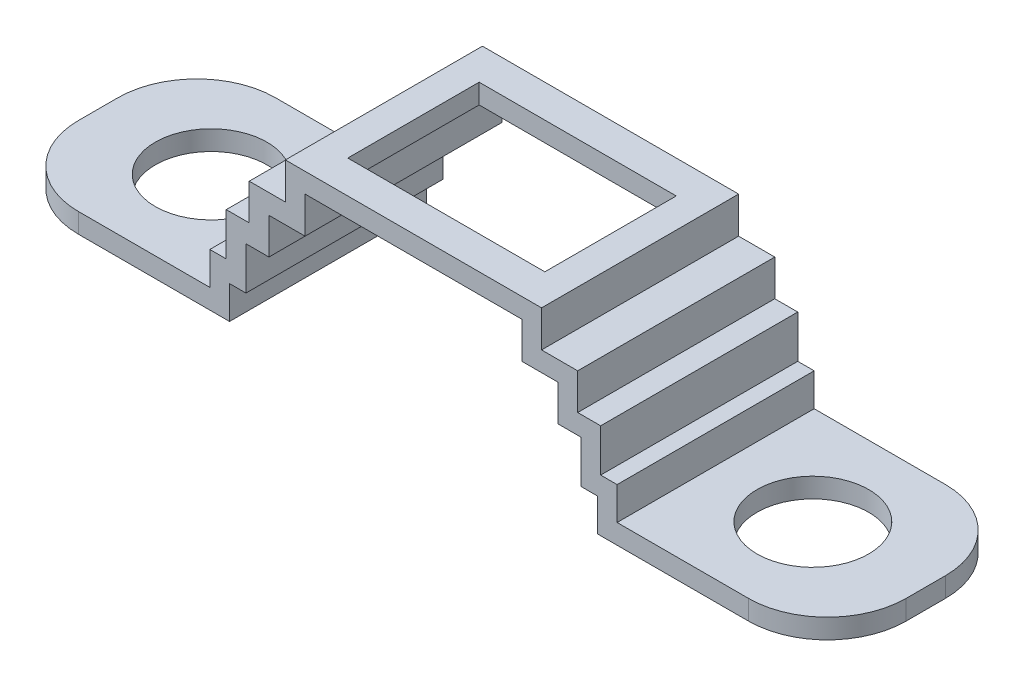
SolidWorks part; units mm, degrees
material "PBT General Purpose"
ref_plane "Front Plane" through (0, 0, 0) normal (0, 0, 1) x (1, 0, 0)
ref_plane "Top Plane" through (0, 0, 0) normal (0, 1, 0) x (1, 0, 0)
ref_plane "Right Plane" through (0, 0, 0) normal (1, 0, 0) x (0, 0, -1)
sketch "Sketch1" plane through (0, 0, 0) normal (0, 0, 1) x (1, 0, 0)
  line L0 (-63, 4.5) -> (-28, 4.5)
  line L1 (-28, 4.5) -> (-28, 9.5)
  line L2 (-28, 9.5) -> (-25.5, 9.5)
  line L3 (-25.5, 9.5) -> (-25.5, 16)
  line L4 (-25.5, 16) -> (-22, 16)
  line L5 (-22, 16) -> (-22, 21.5)
  line L6 (-22, 21.5) -> (-16.5, 21.5)
  line L7 (-16.5, 21.5) -> (-16.5, 27.05)
  line L8 (-16.5, 27.05) -> (0, 27.05)
  circle A0 centre (0, 0) radius 27.05
  dimension "D1" = 54.1
  dimension "D2" = 35
  dimension "D3" = 4.5
  dimension "D4" = 28
  dimension "D5" = 5
  dimension "D6" = 2.5
  dimension "D7" = 6.5
  dimension "D8" = 3.5
  dimension "D9" = 5.5
  dimension "D10" = 5.5
  dimension "D11" = 16.5
  dimension "D12" = 5.55
extrude "Extrude-Thin1" add sketch "Sketch1" along normal mid plane 30 thin contours L0 L1 L2 L3 L4 L5 L6 L7 L8 thin type one direction reverse wall 3
sketch "Sketch2" plane through (0, 7.5, 0) normal (0, 1, 0) x (1, 0, 0)
  line L0 (0, -15) -> (0, 15) construction
  circle A0 centre (-45.8, 0) radius 8.5
  dimension "D1" = 17
  dimension "D2" = 45.8
extrude "Cut-Extrude1" cut sketch "Sketch2" against normal through all
fillet "Fillet1" radius 12 2 edges at (-63, 6, -15) (-63, 6, 15)
mirror "Mirror1" about plane through (0, 30.05, 15) normal (1, 0, 0) of "Fillet1", "Cut-Extrude1", "Extrude-Thin1"
sketch "Sketch3" plane through (0, 30.05, 0) normal (0, 1, 0) x (1, 0, 0)
  line L1 (15, -10) -> (-15, -10)
  line L2 (15, -10) -> (15, 10)
  line L3 (15, 10) -> (-15, 10)
  line L4 (-15, -10) -> (-15, 10)
  line L5 (15, -10) -> (-15, 10) construction
  line L6 (15, 10) -> (-15, -10) construction
  point P0 (0, 0)
  dimension "D1" = 30
  dimension "D2" = 20
extrude "Cut-Extrude2" cut sketch "Sketch3" against normal through all
